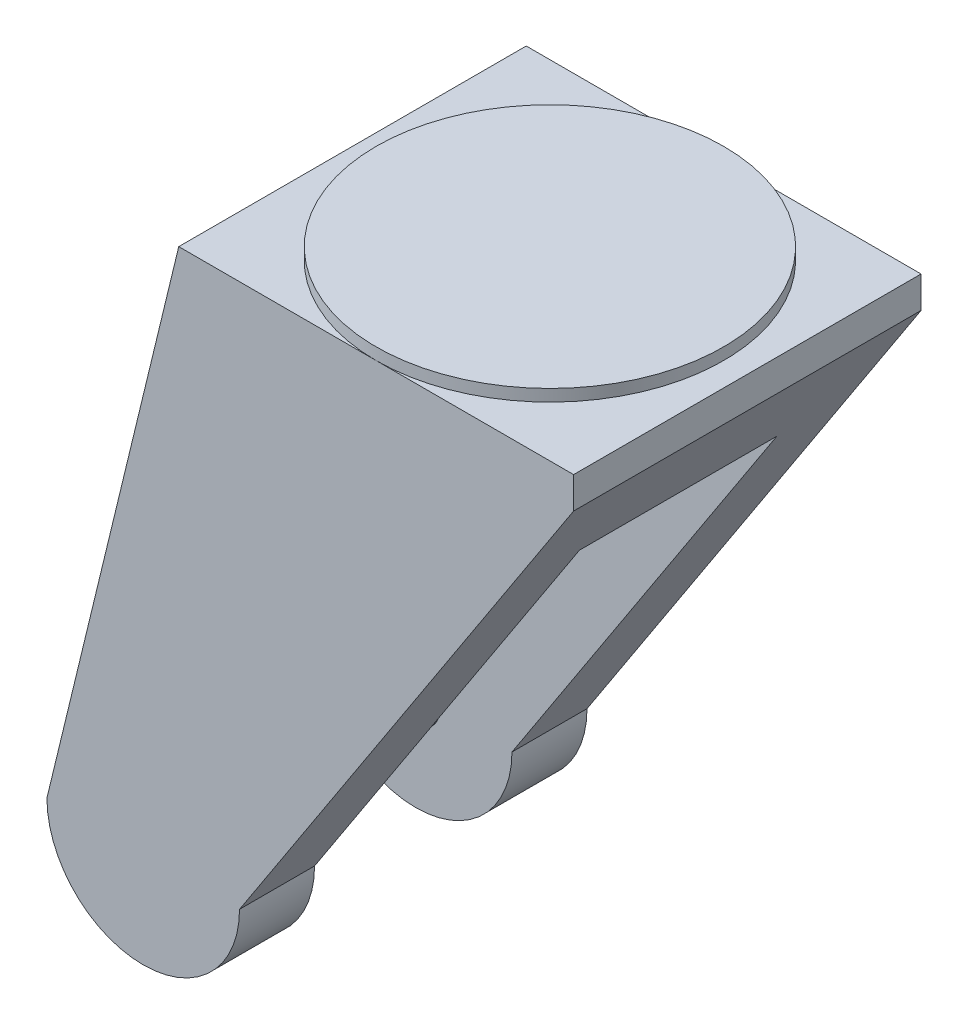
SolidWorks part; units mm, degrees
material "Acciaio al carbonio semplice"
ref_plane "Piano frontale" through (0, 0, 0) normal (0, 0, 1) x (1, 0, 0)
ref_plane "Piano superiore" through (0, 0, 0) normal (0, 1, 0) x (1, 0, 0)
ref_plane "Piano destro" through (0, 0, 0) normal (1, 0, 0) x (0, 0, -1)
sketch "Schizzo1" plane through (0, 0, 0) normal (0, 0, 1) x (1, 0, 0)
  line L0 (-50, 4) -> (-83.39, -133.65)
  line L1 (-50, 4) -> (50, 4)
  line L2 (-50, 4) -> (-50, -4) construction
  line L3 (-50, -4) -> (50, -4) construction
  line L4 (50, 4) -> (50, -4)
  line L5 (-50, 4) -> (50, -4) construction
  line L6 (-50, -4) -> (50, 4) construction
  line L7 (50, -4) -> (-34.61, -133.65)
  line L8 (-83.39, -133.65) -> (-34.61, -133.65) construction
  circle A0 centre (-59, -133.65) radius 100 construction
  circle A1 centre (-59, -133.65) radius 6.05 construction
  arc A2 (-83.39, -133.65) -> (-34.61, -133.65) centre (-59, -133.65) ccw
  point P0 (0, 0)
  point P7 (-50, 7)
  point P9 (-59, -133.65)
  point P10 (0, 4)
  dimension "D2" = 200
  dimension "D5" = 12.1
  dimension "D1" = 59
  dimension "D3" = 140.65
  dimension "D4" = 3
  dimension "D6" = 100
  dimension "D7" = 8
  dimension "D8" = 48.78
extrude "Estrusione-Estrusione1" add sketch "Schizzo1" along normal blind 88
sketch "Schizzo2" plane through (0, 0, 0) normal (1, 0, 0) x (0, 0, -1)
  line L0 (-44, 4) -> (-44, -158.04) construction
  line L1 (-69, -45.845) -> (-19, -45.845) construction
  line L2 (-69, -45.845) -> (-69, -245.845)
  line L3 (-69, -245.845) -> (-19, -245.845)
  line L4 (-19, -45.845) -> (-19, -245.845)
  line L5 (-69, -45.845) -> (-19, -245.845) construction
  line L6 (-69, -245.845) -> (-19, -45.845) construction
  line L7 (-88, 4) -> (0, 4) construction
  line L8 (-88, -158.04) -> (0, -158.04) construction
  line L9 (-88, -158.04) -> (0, -158.04) construction
  line L10 (-69, -45.845) -> (-69, -30.845)
  line L11 (-69, -30.845) -> (-19, -30.845)
  line L12 (-19, -30.845) -> (-19, -45.845)
  point P0 (-44, -145.845)
  dimension "D1" = 200
  dimension "D2" = 50
  dimension "D3" = 12.195
  dimension "D4" = 15
extrude "Taglio-Estrusione2" cut sketch "Schizzo2" against normal through all both and the other way through all
sketch "Schizzo4" plane through (0, 0, 88) normal (0, 0, 1) x (1, 0, 0)
  circle A0 centre (-59, -133.65) radius 6.05
  dimension "D1" = 12.1
extrude "Estrusione-Estrusione2" add sketch "Schizzo4" against normal up to surface (69 mm away) up to face at (-35.9929, -88.345, 19)
sketch "Schizzo6" plane through (0, 4, 0) normal (0, 1, 0) x (1, 0, 0)
  line L0 (-50, -44) -> (50, -44) construction
  line L1 (-50, -88) -> (-50, 0) construction
  line L2 (50, -88) -> (50, 0) construction
  circle A1 centre (0, -44) radius 44
extrude "Estrusione-Estrusione3" add sketch "Schizzo6" along normal blind 3
sketch "Schizzo8" plane through (0, 7, 0) normal (0, 1, 0) x (1, 0, 0)
  line L0 (-50, -44) -> (50, -44) construction
  line L1 (-50, -88) -> (-50, 0) construction
  line L2 (50, -88) -> (50, 0) construction
  line L3 (0, 0) -> (0, -88) construction
  point P0 (0, -44)
ref_point "Punto1"
ref_axis "Assi1" through (0, 54.698, 44) along (0, -1, 0)
